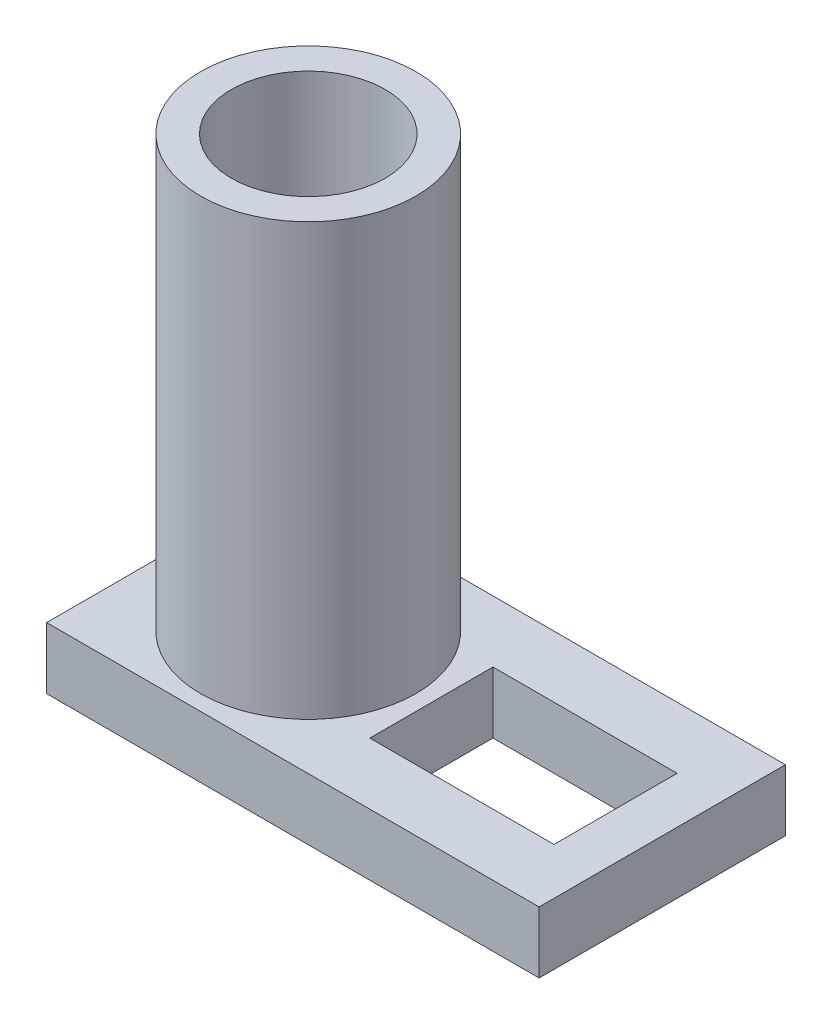
SolidWorks part; units mm, degrees
ref_plane "Спереди" through (0, 0, 0) normal (0, 0, 1) x (1, 0, 0)
ref_plane "Сверху" through (0, 0, 0) normal (0, 1, 0) x (1, 0, 0)
ref_plane "Справа" through (0, 0, 0) normal (1, 0, 0) x (0, 0, -1)
sketch "Эскиз1" plane through (0, 0, 0) normal (0, 1, 0) x (1, 0, 0)
  line L1 (-45, -40) -> (115, -40)
  line L2 (-45, -40) -> (-45, 40)
  line L3 (-45, 40) -> (115, 40)
  line L4 (115, -40) -> (115, 40)
  line L5 (-45, -40) -> (115, 40) construction
  line L6 (-45, 40) -> (115, -40) construction
  line L7 (40, -20) -> (99.8352, -20)
  line L8 (40, -20) -> (40, 20)
  line L9 (40, 20) -> (99.8352, 20)
  line L10 (99.8352, -20) -> (99.8352, 20)
  point P0 (35, 0)
  point P9 (0, 0)
  point P10 (0, 0)
  point P12 (0, 0)
extrude "Бобышка-Вытянуть1" add sketch "Эскиз1" along normal blind 20
sketch "Эскиз3" plane through (0, 20, 0) normal (0, 1, 0) x (1, 0, 0)
  circle A0 centre (0, 0) radius 35
extrude "Вытянуть-Тонкостенный1" add sketch "Эскиз3" along normal blind 140 thin thin type one direction reverse wall 10
